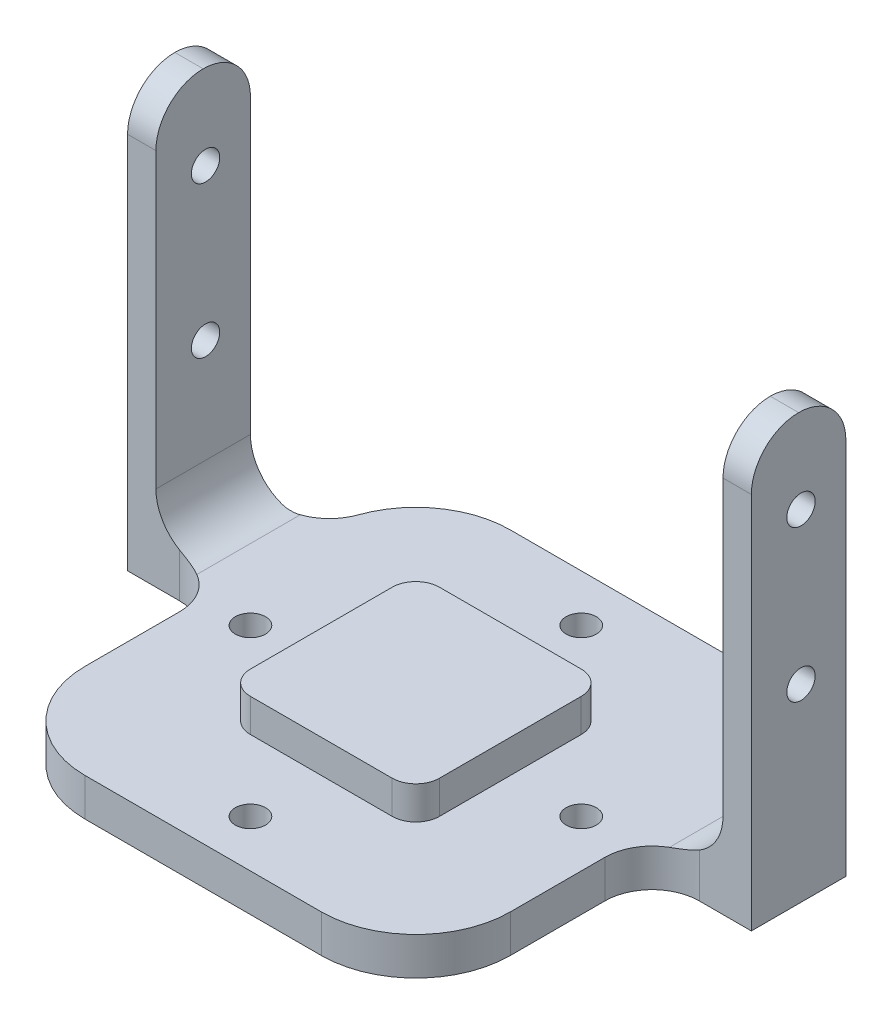
SolidWorks part; units mm, degrees
ref_plane "Front Plane" through (0, 0, 0) normal (0, 0, 1) x (1, 0, 0)
ref_plane "Top Plane" through (0, 0, 0) normal (0, 1, 0) x (1, 0, 0)
ref_plane "Right Plane" through (0, 0, 0) normal (1, 0, 0) x (0, 0, -1)
sketch "Sketch1" plane through (0, 0, 0) normal (0, 1, 0) x (1, 0, 0)
  line L1 (-12.5, 22.5) -> (12.5, 22.5)
  line L2 (-22.5, 12.5) -> (-22.5, -12.5)
  line L3 (-12.5, -22.5) -> (12.5, -22.5)
  line L4 (22.5, 12.5) -> (22.5, -12.5)
  line L5 (-22.5, 22.5) -> (22.5, -22.5) construction
  line L6 (-22.5, -22.5) -> (22.5, 22.5) construction
  circle A0 centre (-17.5, 0) radius 1.6
  circle A2 centre (0, 17.5) radius 1.6
  circle A3 centre (17.5, 0) radius 1.6
  circle A4 centre (0, -17.5) radius 1.6
  arc A5 (12.5, -22.5) -> (22.5, -12.5) centre (12.5, -12.5) ccw
  arc A6 (-22.5, -12.5) -> (-12.5, -22.5) centre (-12.5, -12.5) ccw
  arc A7 (12.5, 22.5) -> (22.5, 12.5) centre (12.5, 12.5) cw
  arc A8 (-12.5, 22.5) -> (-22.5, 12.5) centre (-12.5, 12.5) ccw
  point P0 (0, 0)
  point P17 (0, 0)
  dimension "D1" = 17.5
  dimension "D2" = 3.2
  dimension "D5" = 10
  dimension "D4" = 45
  dimension "D3" = 4
extrude "Boss-Extrude1" add sketch "Sketch1" along normal blind 4
sketch "Sketch2" plane through (-22.5, 0, 0) normal (-1, 0, 0) x (0, 0, 1)
  line L0 (0, 0) -> (0, -11.8168) construction
  line L1 (-12.5, 0) -> (-2.5, 0)
  line L2 (-12.5, 0) -> (-12.5, 45)
  line L3 (-12.5, 45) -> (-2.5, 45)
  line L4 (-2.5, 0) -> (-2.5, 45)
  line L6 (-12.5, 0) -> (12.5, 0) construction
  circle A0 centre (-7.75, 36) radius 1.5
  circle A1 centre (-7.75, 20) radius 1.5
  point P13 (0, 0)
  point P14 (0, 0)
  dimension "D3" = 16
  dimension "D4" = 3
  dimension "D1" = 45
  dimension "D2" = 10
  dimension "D5" = 20
  dimension "D6" = 7.75
extrude "Boss-Extrude2" add sketch "Sketch2" along normal blind 3 from offset 7.5 separate body
sketch "Sketch3" plane through (-22.5, 0, 0) normal (-1, 0, 0) x (0, 0, 1)
  line L0 (-2.5, 0) -> (-2.5, 45) construction
  line L1 (-2.5, 0) -> (-2.5, 45) construction
  line L3 (-12.5, 4) -> (-2.5, 4)
  line L4 (-12.5, 4) -> (-12.5, 0)
  line L5 (-12.5, 0) -> (-2.5, 0)
  line L6 (-2.5, 4) -> (-2.5, 0)
extrude "Boss-Extrude3" add sketch "Sketch3" along normal up to next
fillet "Fillet4" radius 5 2 edges at (-22.5, 2, -12.5) (-22.5, 2, -2.5)
fillet "Fillet5" radius 5 3 edges at (-31.5, 45, -2.5) (-31.5, 45, -12.5) (-30, 4, -7.5)
mirror "Mirror8" about plane through (0, 0, 0) normal (1, 0, 0) of bodies 103
sketch "Sketch4" plane through (0, 4, 0) normal (0, 1, 0) x (1, 0, 0)
  line L1 (-7.5, 10) -> (7.5, 10)
  line L2 (-10, 7.5) -> (-10, -7.5)
  line L3 (-7.5, -10) -> (7.5, -10)
  line L4 (10, 7.5) -> (10, -7.5)
  line L5 (-10, 10) -> (10, -10) construction
  line L6 (-10, -10) -> (10, 10) construction
  arc A0 (7.5, -10) -> (10, -7.5) centre (7.5, -7.5) ccw
  arc A1 (-10, -7.5) -> (-7.5, -10) centre (-7.5, -7.5) ccw
  arc A2 (7.5, 10) -> (10, 7.5) centre (7.5, 7.5) cw
  arc A3 (-7.5, 10) -> (-10, 7.5) centre (-7.5, 7.5) ccw
  point P0 (0, 0)
  dimension "D3" = 2.5
  dimension "D1" = 20
  dimension "D2" = 20
extrude "Boss-Extrude4" add sketch "Sketch4" along normal blind 3.5
